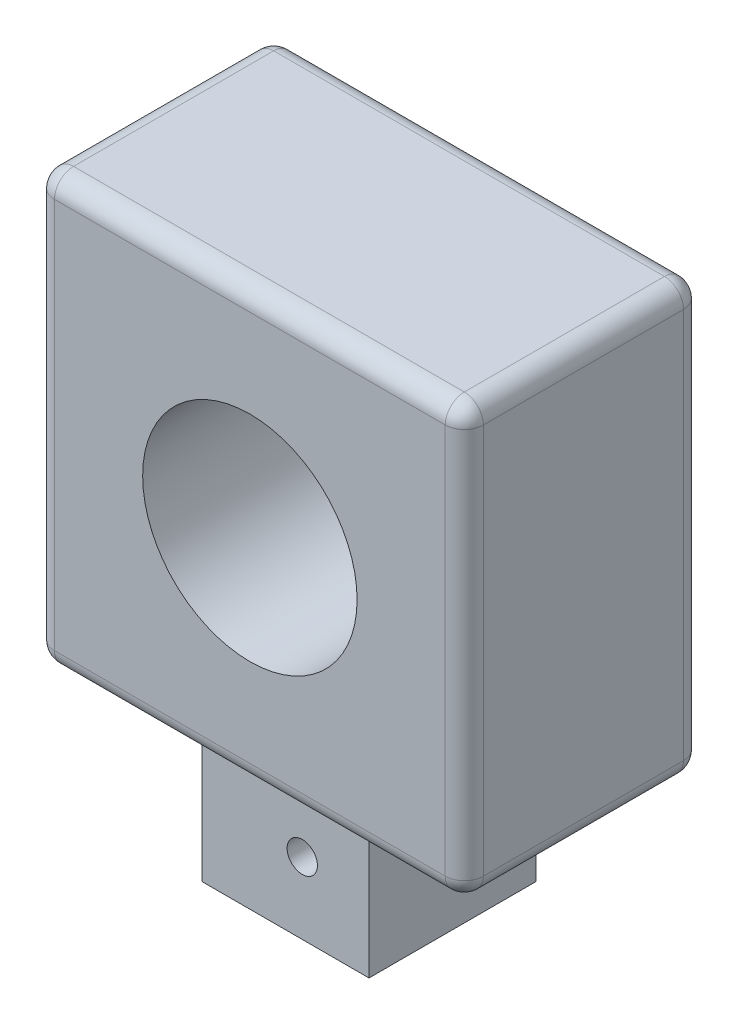
SolidWorks part; units mm, degrees
ref_plane "Front Plane" through (0, 0, 0) normal (0, 0, 1) x (1, 0, 0)
ref_plane "Top Plane" through (0, 0, 0) normal (0, 1, 0) x (1, 0, 0)
ref_plane "Right Plane" through (0, 0, 0) normal (1, 0, 0) x (0, 0, -1)
sketch "Sketch1" plane through (0, 0, 0) normal (0, 1, 0) x (1, 0, 0)
  line L1 (-11.1125, -11.1125) -> (11.1125, -11.1125)
  line L2 (-11.1125, -11.1125) -> (-11.1125, 11.1125)
  line L3 (-11.1125, 11.1125) -> (11.1125, 11.1125)
  line L4 (11.1125, -11.1125) -> (11.1125, 11.1125)
  line L5 (-11.1125, -11.1125) -> (11.1125, 11.1125) construction
  line L6 (-11.1125, 11.1125) -> (11.1125, -11.1125) construction
  point P0 (0, 0)
  dimension "D1" = 22.225
  dimension "D2" = 22.225
extrude "Boss-Extrude1" add sketch "Sketch1" along normal blind 12.7 and the other way blind 6.35
sketch "Sketch2" plane through (0, 12.7, 0) normal (0, 1, 0) x (1, 0, 0)
  line L1 (-28.575, -15.875) -> (28.575, -15.875)
  line L2 (-28.575, -15.875) -> (-28.575, 15.875)
  line L3 (-28.575, 15.875) -> (28.575, 15.875)
  line L4 (28.575, -15.875) -> (28.575, 15.875)
  line L5 (-28.575, -15.875) -> (28.575, 15.875) construction
  line L6 (-28.575, 15.875) -> (28.575, -15.875) construction
  point P0 (0, 0)
  dimension "D1" = 57.15
  dimension "D2" = 31.75
extrude "Boss-Extrude2" add sketch "Sketch2" along normal blind 57.15
sketch "Sketch3" plane through (0, 0, 15.875) normal (0, 0, 1) x (1, 0, 0)
  line L0 (-28.575, 69.85) -> (28.575, 69.85) construction
  line L1 (28.575, 69.85) -> (28.575, 12.7) construction
  circle A0 centre (0, 41.275) radius 14.2875
  dimension "D1" = 28.575
  dimension "D2" = 28.575
  dimension "D3" = 28.575
extrude "Cut-Extrude1" cut sketch "Sketch3" against normal through all
fillet "Fillet1" radius 2.54 12 edges at (28.575, 69.85, 0) (28.575, 12.7, 0) (-28.575, 69.85, 0) (-28.575, 12.7, 0) (28.575, 41.275, -15.875) (0, 69.85, -15.875) (-28.575, 41.275, -15.875) (0, 12.7, -15.875) (-28.575, 41.275, 15.875) (0, 69.85, 15.875) (28.575, 41.275, 15.875) (0, 12.7, 15.875)
sketch "Sketch4" plane through (0, 0, -11.1125) normal (0, 0, -1) x (-1, 0, 0)
  line L0 (-11.1125, -6.35) -> (11.1125, -6.35) construction
  line L1 (-11.1125, -6.35) -> (-11.1125, 12.7) construction
  circle A0 centre (-2.2225, 3.175) radius 2.0193
  dimension "D1" = 4.0386
  dimension "D2" = 9.525
  dimension "D3" = 8.89
extrude "Cut-Extrude2" cut sketch "Sketch4" against normal through all
